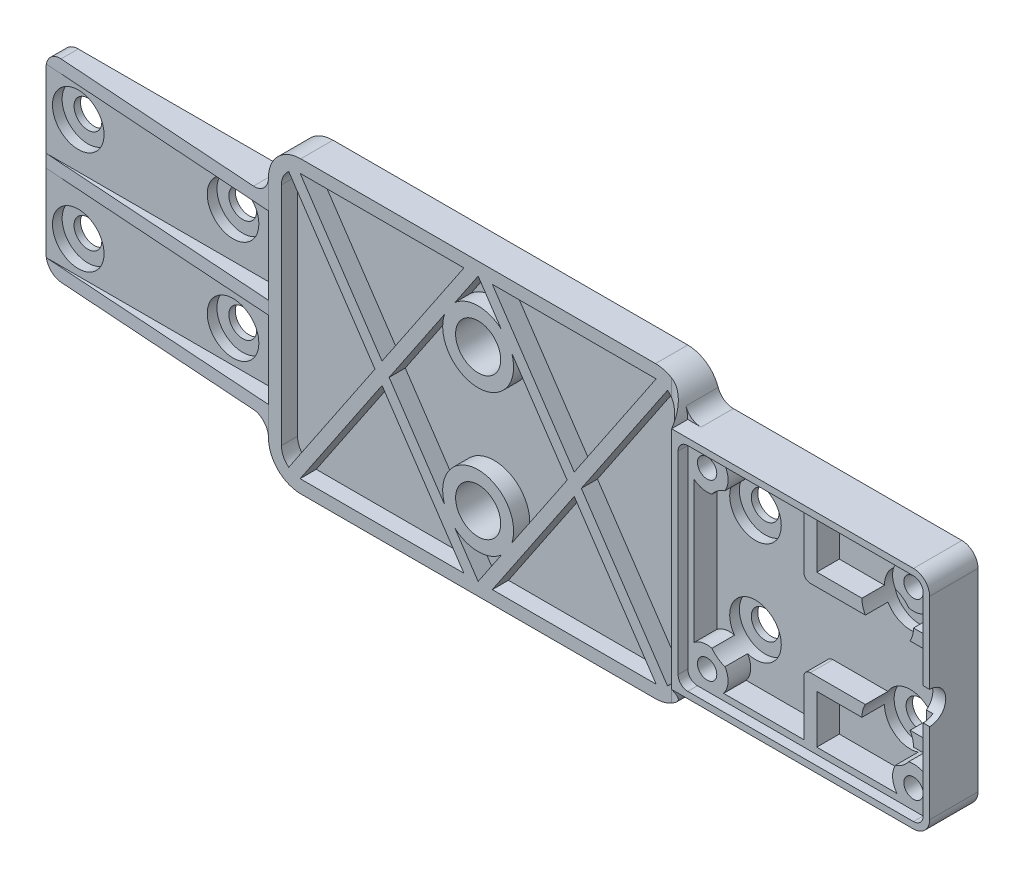
SolidWorks part; units mm, degrees
ref_plane "Face" through (0, 0, 0) normal (0, 0, 1) x (1, 0, 0)
ref_plane "Dessus" through (0, 0, 0) normal (0, 1, 0) x (1, 0, 0)
ref_plane "Droite" through (0, 0, 0) normal (1, 0, 0) x (0, 0, -1)
sketch "Esquisse1" plane through (0, 0, 0) normal (0, 0, 1) x (1, 0, 0)
  line L0 (0, 15) -> (0, -15) construction
  line L1 (-71, -15) -> (-34, -15)
  line L2 (-71, -15) -> (-71, 15)
  line L3 (-71, 15) -> (-34, 15)
  line L4 (71, -17.5) -> (71, 17.5)
  line L5 (71, 0) -> (-71, 0) construction
  line L6 (-1.5, 22.5) -> (-1.5, -22.5) construction
  line L10 (31, -17.5) -> (71, -17.5)
  line L11 (-34, 22.5) -> (31, 22.5)
  line L12 (-34, 22.5) -> (-34, 15)
  line L13 (-34, -22.5) -> (31, -22.5)
  line L14 (31, 22.5) -> (31, 17.5)
  line L15 (-34, -15) -> (-34, -22.5)
  line L16 (31, -17.5) -> (31, -22.5)
  line L17 (31, 17.5) -> (71, 17.5)
  circle A2 centre (-1.5, 11) radius 3.5
  circle A3 centre (-1.5, -11) radius 3.5
  point P0 (0, 0)
  point P29 (0, 0)
  dimension "D3" = 7.5
  dimension "D4" = 7.5
  dimension "D5" = 30
  dimension "D6" = 7
  dimension "D8" = 11
  dimension "D2" = 35
  dimension "D7" = 11
  dimension "D9" = 65
  dimension "D10" = 40
  dimension "D11" = 37
  dimension "D12" = 37
extrude "Boss.-Extru.1" add sketch "Esquisse1" against normal blind 2.5
hole_wizard "Chambrage pour vis à six pans creux M41" positions "Esquisse2" profile "Esquisse3" counterbore size "M4" standard "ISO" end condition up to next
sketch "Esquisse2" plane through (0, 0, 0) normal (0, 0, 1) x (1, 0, 0)
  line L1 (-66, 8) -> (-42, 8) construction
  line L2 (-66, 8) -> (-66, -8) construction
  line L3 (-66, -8) -> (-42, -8) construction
  line L4 (-42, 8) -> (-42, -8) construction
  line L6 (39, 8) -> (63, 8) construction
  line L7 (39, 8) -> (39, -8) construction
  line L8 (39, -8) -> (63, -8) construction
  line L9 (63, 8) -> (63, -8) construction
  line L10 (-34, 15) -> (-71, 15) construction
  line L11 (-71, 15) -> (-71, -15) construction
  point P0 (-66, 8)
  point P3 (-42, 8)
  point P6 (-42, -8)
  point P9 (-66, -8)
  point P12 (39, -8)
  point P15 (63, -8)
  point P18 (63, 8)
  point P21 (39, 8)
  dimension "D1" = 24
  dimension "D2" = 16
  dimension "D3" = 7
  dimension "D4" = 5
  dimension "D5" = 81
sketch "Esquisse3" plane through (-66, 8, 0) normal (1, 0, 0) x (0, -1, 0)
  line L0 (0, 0) -> (0, 2.5)
  line L1 (0, 2.5) -> (2.15, 2.5)
  line L3 (2.15, 2.5) -> (2.15, 1.5)
  line L4 (2.15, 1.5) -> (4, 1.5)
  line L5 (4, 1.5) -> (4, 0)
  line L7 (4, 0) -> (0, 0)
  line L11 (0, -6.35) -> (0, 107.95) construction
  dimension "Diamètre du perçage jusqu'au prochain" = 4.3
  dimension "Profondeur du perçage jusqu'au prochain" = 2.5
  dimension "Diamètre du chambrage" = 8
  dimension "Profondeur du chambrage" = 1.5
fillet "Congé1" radius 5 4 edges at (31, 22.5, -1.25) (-34, 22.5, -1.25) (31, -22.5, -1.25) (-34, -22.5, -1.25)
sketch "Point milieu" plane through (0, 0, 0) normal (0, 0, 1) x (1, 0, 0)
  point P0 (0, 0)
sketch "Esquisse5" plane through (0, 0, 0) normal (0, 0, 1) x (1, 0, 0)
  line L0 (71, -17.5) -> (71, 17.5) construction
  line L4 (69, 15.5) -> (69, 8)
  line L5 (71, 0) -> (33, 0) construction
  line L7 (31, 17.5) -> (31, -17.5)
  line L10 (69, 15.5) -> (33, 15.5)
  line L12 (31, -17.5) -> (71, -17.5)
  line L14 (33, -15.5) -> (69, -15.5)
  line L15 (71, -17.5) -> (71, 17.5)
  line L19 (33, 15.5) -> (33, -15.5)
  line L20 (31, 17.5) -> (71, 17.5)
  line L21 (71, 17.5) -> (31, 17.5) construction
  line L22 (69, 8) -> (67, 8) construction
  line L24 (66.4641, 6) -> (69, 6) construction
  line L25 (69, 6) -> (69, -6)
  line L26 (66.4641, -6) -> (69, -6) construction
  line L28 (69, -8) -> (67, -8) construction
  line L29 (69, -8) -> (69, -15.5)
  line L30 (69, 8) -> (69, 6)
  line L31 (69, -6) -> (69, -8)
  arc A2 (66.4641, 6) -> (67, 8) centre (63, 8) ccw construction
  arc A3 (67, -8) -> (66.4641, -6) centre (63, -8) ccw construction
  circle A4 centre (63, 8) radius 4 construction
  circle A5 centre (63, -8) radius 4 construction
  dimension "D1" = 2
  dimension "D2" = 2
  dimension "D3" = 2
  dimension "D4" = 2
  dimension "D5" = 2
  dimension "D7" = 12
extrude "Boss.-Extru.2" add sketch "Esquisse5" along normal blind 5
sketch "Esquisse6" plane through (71, 0, 0) normal (-1, 0, 0) x (0, 0, 1)
  line L1 (5, 2.5) -> (5, -2.5)
  line L3 (5, -17.5) -> (5, 17.5) construction
  arc A0 (5, 2.5) -> (5, -2.5) centre (5, 0) ccw
  dimension "D1" = 2.5
extrude "Trou Axe Moteur" cut sketch "Esquisse6" along normal up to next
sketch "Esquisse8" plane through (0, 0, 0) normal (0, 0, 1) x (1, 0, 0)
  line L0 (35, 0) -> (51, 0) construction
  line L5 (51, 0) -> (67, 0) construction
  line L6 (35, 13.5) -> (35, -13.5) construction
  line L7 (35, 0) -> (33, 0) construction
  line L8 (51, -15.5) -> (51, 15.5) construction
  line L9 (67, 13.5) -> (67, -13.5) construction
  line L10 (71, 0) -> (33.7792, 0) construction
  line L11 (33, 15.5) -> (33, -15.5) construction
  line L12 (67, -13.5) -> (35, -13.5) construction
  line L13 (31, 17.5) -> (31, -17.5) construction
  line L14 (33, -15.5) -> (69, -15.5) construction
  line L16 (69, 8) -> (67, 8)
  line L20 (69, 15.5) -> (33, 15.5) construction
  line L25 (33, 10.9383) -> (33, 15.5)
  line L27 (69, 15.5) -> (33, 15.5) construction
  line L28 (33, -15.5) -> (33, -10.9383)
  line L29 (33, -15.5) -> (37.5617, -15.5)
  line L32 (69, 15.5) -> (64.4383, 15.5)
  line L33 (69, 10.9383) -> (69, 15.5)
  line L34 (37.5617, 15.5) -> (33, 15.5)
  line L35 (69, -15.5) -> (69, -10.9383)
  line L36 (52, 15.5) -> (50, 15.5)
  line L37 (64.4383, -15.5) -> (69, -15.5)
  line L38 (31, -17.5) -> (71, -17.5) construction
  line L39 (66.4641, 6) -> (69, 6)
  line L40 (52, -15.5) -> (50, -15.5)
  line L41 (50, -7) -> (50, -15.5)
  line L42 (66.4641, -6) -> (69, -6)
  line L43 (52, -8) -> (52, -15.5)
  line L44 (35, -13.5) -> (35, -17.25) construction
  line L45 (35, -13.5) -> (31.25, -13.5) construction
  line L46 (69, -8) -> (67, -8)
  line L55 (50, 7) -> (50, 15.5)
  line L56 (69, -15.5) -> (69, -2.5) construction
  line L57 (63, -8) -> (66.4641, -6) construction
  line L58 (52, 8) -> (52, 15.5)
  line L61 (59, 8) -> (52, 8)
  line L64 (59.5359, 6) -> (51, 6)
  line L65 (59, -8) -> (52, -8)
  line L66 (59.5359, -6) -> (51, -6)
  line L67 (63, 8) -> (66.4641, 6) construction
  line L68 (69, -15.5) -> (69, -2.5) construction
  line L69 (69, 2.5) -> (69, 15.5) construction
  line L72 (69, 8) -> (69, 6)
  line L73 (69, -6) -> (69, -8)
  arc A0 (33, 10.9383) -> (37.5617, 15.5) centre (35, 13.5) ccw
  arc A1 (37.5617, -15.5) -> (33, -10.9383) centre (35, -13.5) ccw
  arc A2 (64.4383, 15.5) -> (69, 10.9383) centre (67, 13.5) ccw
  arc A3 (69, -10.9383) -> (64.4383, -15.5) centre (67, -13.5) ccw
  circle A6 centre (35, -13.5) radius 1.25 construction
  arc A7 (59, 8) -> (59.5359, 6) centre (63, 8) ccw
  arc A12 (50, 7) -> (51, 6) centre (51, 7) ccw
  circle A13 centre (63, 8) radius 4 construction
  arc A14 (66.4641, 6) -> (67, 8) centre (63, 8) ccw
  circle A15 centre (63, 8) radius 4 construction
  arc A16 (50, -7) -> (51, -6) centre (51, -7) cw
  arc A17 (59, -8) -> (59.5359, -6) centre (63, -8) cw
  arc A18 (67, -8) -> (66.4641, -6) centre (63, -8) ccw
  circle A20 centre (63, -8) radius 4 construction
  point P77 (50, 6)
  point P87 (51, 15.5)
  line M12 (69, -15.5) -> (69, 15.5)
  line M13 (69, 15.5) -> (33, 15.5)
  line M14 (33, 15.5) -> (33, -15.5)
  line M15 (33, -15.5) -> (69, -15.5)
  circle M18 centre (63, 8) radius 4
  circle M19 centre (63, -8) radius 4
  circle M21 centre (39, 8) radius 4
  circle M23 centre (39, -8) radius 4
  line M26 (69, -15.5) -> (69, 15.5)
  dimension "D5" = 2
  dimension "D18" = 2.5
  dimension "D11" = 2
  dimension "D7" = 1
  dimension "D2" = 2
  dimension "D9" = 4
  dimension "D10" = 4
  dimension "D3" = 6
  dimension "D4" = 4
  dimension "D6" = 4
  dimension "D8" = 2
  dimension "D12" = 6
  dimension "D13" = 30
extrude "MIP Moteur" add sketch "Esquisse8" along normal blind 3.5 contours A2 M13 M18 M12 | A0 M14 M21 M13 | A1 M23 M14 M15 | A3 M26 M19 M15 | A16 L41 L43 L65 L66 M15 M19 | L55 A12 L64 L61 L58 M18 M13 | L72 L39 A14 L16 | L73 L46 A18 L42
sketch "Esquisse9" plane through (0, 0, 5) normal (0, 0, 1) x (1, 0, 0)
  circle A0 centre (35, 13.5) radius 1.5
  circle A1 centre (67, 13.5) radius 1.5
  circle A2 centre (67, -13.5) radius 1.5
  circle A3 centre (35, -13.5) radius 1.5
  dimension "D1" = 3
extrude "Enlèv. mat.-Extru.2" cut sketch "Esquisse9" against normal blind 4
sketch "Esquisse14" plane through (0, 0, 0) normal (0, 0, 1) x (1, 0, 0)
  line L9 (-34, 17.5) -> (-34, -17.5)
  line L30 (26.1, 20.5) -> (0.7, 20.5)
  line L31 (-29.1, 20.5) -> (-16.4, 1.6341)
  line L32 (-32, 17.5) -> (-32, -17.5)
  line L33 (31, 17.5) -> (31, -17.5)
  line L34 (-1.5, -20.5) -> (-1.5, -22.5) construction
  line L38 (-34, -15) -> (-34, -17.5) construction
  line L42 (26, 22.5) -> (-29, 22.5)
  line L46 (-29, -22.5) -> (26, -22.5)
  line L48 (-1.5, -20.5) -> (12.3, 0)
  line L51 (0.7, -20.5) -> (26.1, -20.5)
  line L52 (-29.1, -20.5) -> (-3.7, -20.5)
  line L53 (-3.7, 20.5) -> (0.7, 20.5) construction
  line L54 (-30.8633, 19.8512) -> (-17.5, 0)
  line L55 (0.7, -20.5) -> (13.4, -1.6341)
  line L56 (-1.5, 20.5) -> (-1.5, -20.5) construction
  line L57 (-1.5, 20.5) -> (12.3, 0)
  line L58 (0.7, 20.5) -> (13.4, 1.6341)
  line L59 (-30.8633, -19.8512) -> (-17.5, 0)
  line L60 (-29.1, -20.5) -> (-16.4, -1.6341)
  line L61 (-3.7, 20.5) -> (-29.1, 20.5)
  line L62 (-29, -22.5) -> (26, -22.5) construction
  line L63 (-15.3, 0) -> (-1.5, 20.5)
  line L64 (-29, 17.5) -> (26, 17.5) construction
  line L65 (-16.4, 1.6341) -> (-3.7, 20.5)
  line L66 (-15.3, 0) -> (-1.5, -20.5)
  line L67 (-16.4, -1.6341) -> (-3.7, -20.5)
  line L68 (14.5, 0) -> (27.8633, 19.8512)
  line L69 (26, 17.5) -> (26, -17.5) construction
  line L70 (13.4, 1.6341) -> (26.1, 20.5)
  line L71 (14.5, 0) -> (27.8633, -19.8512)
  line L72 (13.4, -1.6341) -> (26.1, -20.5)
  line L73 (26, -17.5) -> (-29, -17.5) construction
  line L74 (-29, -17.5) -> (-29, 17.5) construction
  line L75 (29, -17.5) -> (29, 17.5)
  line L76 (-15.3, 0) -> (12.3, 0) construction
  line L77 (31, 17.5) -> (31, -17.5) construction
  line L78 (26, 22.5) -> (-29, 22.5) construction
  arc A12 (-32, -17.5) -> (-30.8633, -19.8512) centre (-29, -17.5) ccw
  arc A13 (27.8633, -19.8512) -> (29, -17.5) centre (26, -17.5) ccw
  arc A16 (29, 17.5) -> (27.8633, 19.8512) centre (26, 17.5) ccw
  arc A17 (-30.8633, 19.8512) -> (-32, 17.5) centre (-29, 17.5) ccw
  arc A37 (31, 17.5) -> (26, 22.5) centre (26, 17.5) ccw
  arc A38 (-29, 22.5) -> (-34, 17.5) centre (-29, 17.5) ccw
  arc A41 (-34, -17.5) -> (-29, -22.5) centre (-29, -17.5) ccw
  arc A42 (26, -22.5) -> (31, -17.5) centre (26, -17.5) ccw
  point P6 (-1.5, 17.5)
  dimension "D4" = 3
  dimension "D6" = 2
  dimension "D10" = 2
  dimension "D9" = 5
  dimension "D3" = 2
  dimension "D5" = 17.6
  dimension "D2" = 41
  dimension "D7" = 2
  dimension "D8" = 2
  dimension "D12" = 17.6
  dimension "D13" = 32
extrude "Nervures Centre" add sketch "Esquisse14" along normal blind 2.5
sketch "Esquisse18" plane through (0, 0, 0) normal (0, 0, 1) x (1, 0, 0)
  circle A0 centre (-1.5, 11) radius 3.5 construction
  circle A1 centre (-1.5, -11) radius 3.5 construction
  circle A2 centre (-1.5, 11) radius 3.5
  circle A3 centre (-1.5, -11) radius 3.5
  circle A4 centre (-1.5, 11) radius 5.5
  circle A5 centre (-1.5, -11) radius 5.5
  dimension "D1" = 2
  dimension "D2" = 2
extrude "Boss.-Extru.5" add sketch "Esquisse18" along normal up to surface (2.5 mm away) contours A4 | A5 | A2 | A3 up to face at (-28.753, 0, 2.5)
sketch "Esquisse15" plane through (0, 0, 0) normal (0, 1, 0) x (1, 0, 0)
  line L0 (-34, -2.5) -> (-71, 0)
  line L1 (-71, 0) -> (-34, 0)
  line L2 (-34, 0) -> (-34, -2.5)
  line L3 (-34, -2.5) -> (-34, 2.5) construction
extrude "Nervure Lat" add sketch "Esquisse15" along normal blind 1 and the other way blind 1
pattern_linear "Répétition linéaire1" count 2 spacing 14 along (0, -1, 0) count 2 spacing 14 along (0, 1, 0) of "Nervure Lat"
fillet "Congé3" radius 2.5 8 edges at (-34, -15, 0) (-34, 15, 0) (-71, 15, -1.25) (-71, -15, -1.25) (71, 17.5, 1.25) (71, -17.5, 1.25) (31, -17.5, 0) (31, 17.5, 0)
fillet "Congé4" radius 2.5 1 edges at (31, 0, 2.5)
sketch "Esquisse16" plane through (0, 0, 5) normal (0, 0, 1) x (1, 0, 0)
  line L0 (69, 2.5) -> (69, -2.5)
  line L1 (70, 2.5) -> (70, -2.5)
  line L6 (69, 2.5) -> (69, 15)
  line L7 (68.5, 15.5) -> (33.5, 15.5)
  line L8 (33, 15) -> (33, -15)
  line L9 (33.5, -15.5) -> (68.5, -15.5)
  line L10 (69, -15) -> (69, -2.5)
  line L12 (68.5, 17.5) -> (31, 17.5) construction
  line L13 (71, 2.5) -> (71, 15) construction
  line L15 (71, -15) -> (71, -2.5) construction
  line L16 (31, -17.5) -> (68.5, -17.5) construction
  line L17 (31, 17.5) -> (31, -17.5) construction
  line L18 (32, 15) -> (32, -15)
  line L19 (33.5, -16.5) -> (68.5, -16.5)
  line L20 (68.5, 16.5) -> (33.5, 16.5)
  line L21 (70, -15) -> (70, -2.5)
  line L23 (70, 2.5) -> (70, 15)
  line L24 (32, 16.5) -> (32, -16.5) construction
  line L25 (68.5, 16.5) -> (32, 16.5) construction
  line L26 (32, -16.5) -> (68.5, -16.5) construction
  line L27 (68.5, 15.5) -> (33, 15.5) construction
  line L28 (33, 15.5) -> (33, -15.5) construction
  line L29 (33, -15.5) -> (68.5, -15.5) construction
  line L30 (70, -2.5) -> (70, 2.5) construction
  line L31 (69, -2.5) -> (69, 2.5) construction
  arc A2 (69, 15) -> (68.5, 15.5) centre (68.5, 15) ccw
  arc A3 (68.5, -15.5) -> (69, -15) centre (68.5, -15) ccw
  arc A4 (71, 15) -> (68.5, 17.5) centre (68.5, 15) ccw construction
  arc A6 (70, 15) -> (68.5, 16.5) centre (68.5, 15) ccw
  arc A7 (68.5, -16.5) -> (70, -15) centre (68.5, -15) ccw
  arc A8 (32, 15) -> (33.5, 16.5) centre (33.5, 15) cw
  arc A9 (32, -15) -> (33.5, -16.5) centre (33.5, -15) ccw
  arc A10 (33.5, 15.5) -> (33, 15) centre (33.5, 15) ccw
  arc A11 (33, -15) -> (33.5, -15.5) centre (33.5, -15) ccw
  dimension "D3" = 1.5
  dimension "D4" = 0.5
  dimension "D5" = 1
  dimension "D1" = 1
  dimension "D6" = 1
  dimension "D7" = 5
  dimension "D8" = 1
  dimension "D9" = 1
  dimension "D10" = 1
  dimension "D2" = 1
extrude "Enlèv. mat.-Extru.3" cut sketch "Esquisse16" against normal blind 1.5
